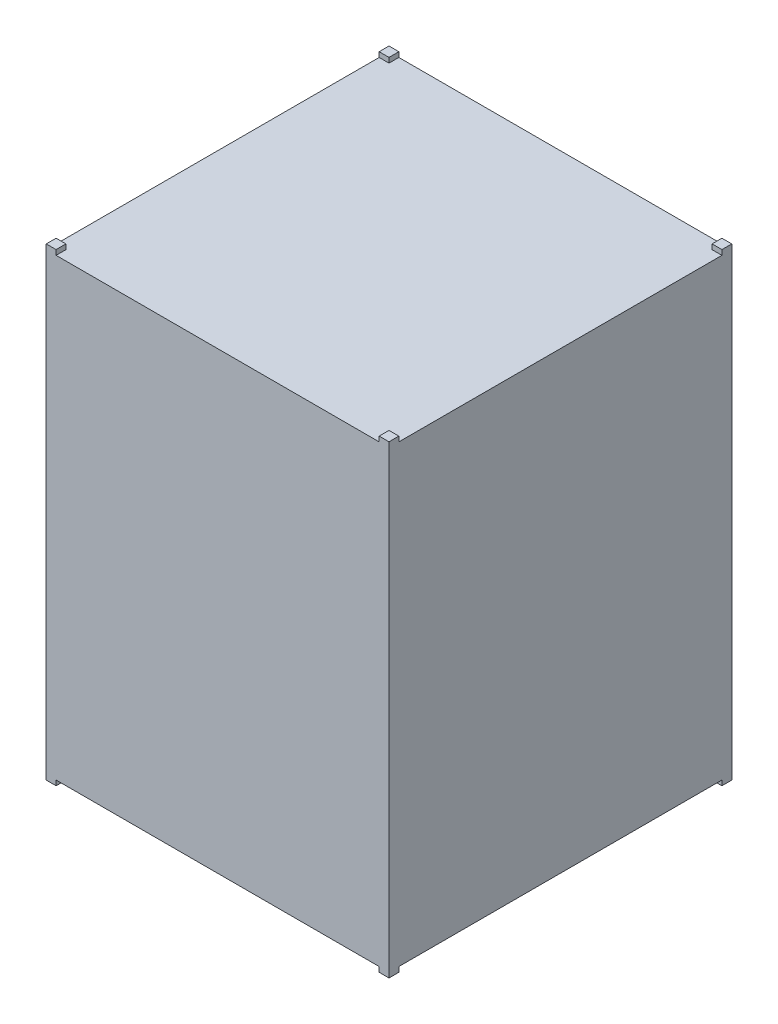
SolidWorks part; units mm, degrees
ref_plane "Piano frontale" through (0, 0, 0) normal (0, 0, 1) x (1, 0, 0)
ref_plane "Piano superiore" through (0, 0, 0) normal (0, 1, 0) x (1, 0, 0)
ref_plane "Piano destro" through (0, 0, 0) normal (1, 0, 0) x (0, 0, -1)
sketch "Schizzo2" plane through (0, 0, 0) normal (0, 1, 0) x (1, 0, 0)
  line L0 (-113.15, 106.65) -> (-113.15, -106.65)
  line L5 (-106.65, 113.15) -> (106.65, 113.15)
  line L6 (113.15, 106.65) -> (113.15, -106.65)
  line L7 (106.65, -113.15) -> (-106.65, -113.15)
  line L10 (-113.15, 106.65) -> (-106.65, 106.65)
  line L11 (-106.65, 113.15) -> (-106.65, 106.65)
  line L14 (-106.65, -113.15) -> (-106.65, -106.65)
  line L15 (-113.15, -106.65) -> (-106.65, -106.65)
  line L16 (113.15, -106.65) -> (106.65, -106.65)
  line L17 (106.65, -113.15) -> (106.65, -106.65)
  line L36 (106.65, 113.15) -> (106.65, 106.65)
  line L37 (106.65, 106.65) -> (113.15, 106.65)
extrude "Estrusione-Estrusione2" add sketch "Schizzo2" along normal blind 150 and the other way blind 150
sketch "Schizzo3" plane through (0, -150, 0) normal (0, -1, 0) x (1, 0, 0)
  line L1 (-106.65, 113.15) -> (-113.15, 113.15)
  line L2 (-106.65, 113.15) -> (-106.65, 106.65)
  line L3 (-106.65, 106.65) -> (-113.15, 106.65)
  line L4 (-113.15, 113.15) -> (-113.15, 106.65)
  line L5 (106.65, 113.15) -> (113.15, 113.15)
  line L6 (106.65, 113.15) -> (106.65, 106.65)
  line L7 (106.65, 106.65) -> (113.15, 106.65)
  line L8 (113.15, 113.15) -> (113.15, 106.65)
  line L9 (106.65, -106.65) -> (113.15, -106.65)
  line L10 (106.65, -106.65) -> (106.65, -113.15)
  line L11 (106.65, -113.15) -> (113.15, -113.15)
  line L12 (113.15, -106.65) -> (113.15, -113.15)
  line L13 (-106.65, -106.65) -> (-113.15, -106.65)
  line L14 (-106.65, -106.65) -> (-106.65, -113.15)
  line L15 (-106.65, -113.15) -> (-113.15, -113.15)
  line L16 (-113.15, -106.65) -> (-113.15, -113.15)
extrude "Estrusione-Estrusione3" add sketch "Schizzo3" along normal blind 3.3 and the other way blind 303.3
